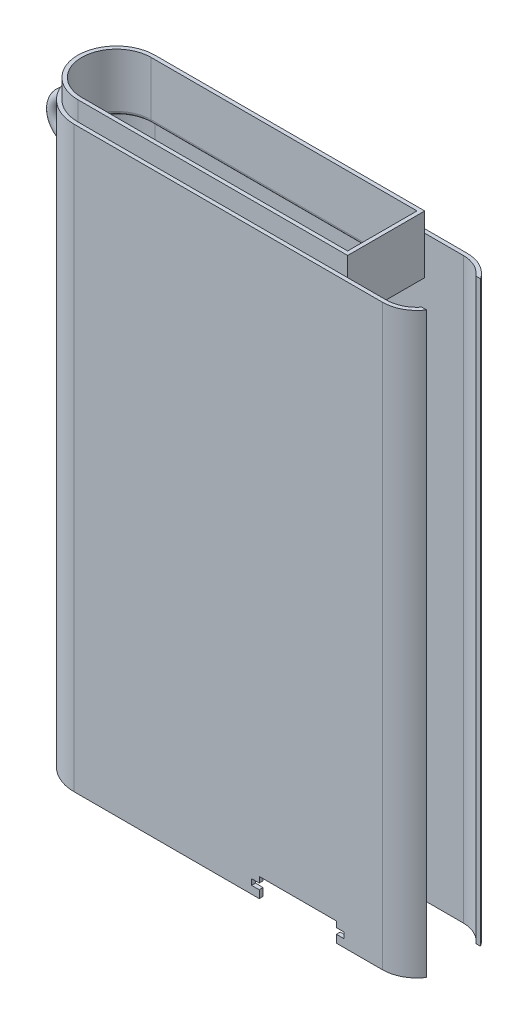
SolidWorks part; units mm, degrees
material "7075-O (SS)"
ref_plane "Front Plane" through (0, 0, 0) normal (0, 0, 1) x (1, 0, 0)
ref_plane "Top Plane" through (0, 0, 0) normal (0, 1, 0) x (1, 0, 0)
ref_plane "Right Plane" through (0, 0, 0) normal (1, 0, 0) x (0, 0, -1)
sketch "Sketch3" plane through (0, 0, 0) normal (0, 1, 0) x (1, 0, 0)
  line L0 (-97.3006, 0) -> (97.3006, 0) construction
  line L1 (0, 66.3624) -> (0, -66.3624) construction
  line L2 (0, 11) -> (80, 11)
  line L3 (0, 10) -> (80, 10)
  line L4 (86.245, 7) -> (87.4833, 7)
  line L5 (0, -10) -> (80, -10)
  line L6 (0, -11) -> (80, -11)
  line L7 (86.245, -7) -> (87.4833, -7)
  line L8 (80, 13.4664) -> (80, -11.4843) construction
  line L9 (86.245, 7) -> (86.245, -7) construction
  line L10 (87.4833, 7) -> (87.4833, -7) construction
  arc A0 (0, 11) -> (0, -11) centre (0, 0) ccw
  arc A1 (0, 10) -> (0, -10) centre (0, 0) ccw
  arc A2 (80, 10) -> (86.245, 7) centre (80, 2) cw
  arc A3 (80, 11) -> (87.4833, 7) centre (80, 2) cw
  arc A4 (80, -10) -> (86.245, -7) centre (80, -2) ccw
  arc A5 (80, -11) -> (87.4833, -7) centre (80, -2) ccw
  dimension "D1" = 11
  dimension "D2" = 10
  dimension "D4" = 8
  dimension "D5" = 9
  dimension "D7" = 8
  dimension "D8" = 9
  dimension "D3" = 80
  dimension "D6" = 7
  dimension "D9" = 7
extrude "Boss-Extrude1" add sketch "Sketch3" along normal blind 150
ref_plane "Plane1" through (0, 140, 0) normal (0, 1, 0) x (1, 0, 0)
sketch "Sketch4" plane through (0, 140, 0) normal (0, 1, 0) x (1, 0, 0)
  line L0 (0, 66.3624) -> (0, -66.3624) construction
  line L1 (0, 10) -> (70, 10)
  line L2 (0, -10) -> (70, -10)
  line L3 (0, 10) -> (80, 10) construction
  line L4 (0, -10) -> (80, -10) construction
  line L5 (70, 10) -> (70, -10)
  line L6 (0, 9) -> (69, 9)
  line L7 (0, -9) -> (69, -9)
  line L8 (69, -9) -> (69, 9)
  arc A0 (0, 10) -> (0, -10) centre (0, 0) ccw
  arc A1 (0, 9) -> (0, -9) centre (0, 0) ccw
  dimension "D3" = 9
  dimension "D1" = 70
  dimension "D2" = 70
  dimension "D4" = 69
extrude "Boss-Extrude2" add sketch "Sketch4" along normal blind 15 separate body
fillet "Fillet9" radius 1 3 edges at (34.5, 140, 9) (-9, 140, 0) (34.5, 140, -9)
sketch "Sketch7" plane through (0, 0, 11) normal (0, 0, 1) x (1, 0, 0)
  line L0 (48.0657, 0) -> (68.0657, 0)
  line L1 (0, 0) -> (80, 0) construction
  line L2 (68.0657, 0) -> (68.0657, 2)
  line L3 (68.0657, 2) -> (70.0657, 2)
  line L4 (70.0657, 2) -> (70.0657, 3.5)
  line L5 (70.0657, 3.5) -> (68.0657, 3.5)
  line L6 (68.0657, 3.5) -> (68.0657, 5)
  line L7 (68.0657, 5) -> (48.0657, 5)
  line L8 (48.0657, 5) -> (48.0657, 3.5)
  line L9 (48.0657, 3.5) -> (46.0657, 3.5)
  line L10 (46.0657, 3.5) -> (46.0657, 2)
  line L11 (46.0657, 2) -> (48.0657, 2)
  line L12 (48.0657, 2) -> (48.0657, 0)
  point P4 (58.0657, 0)
  point P15 (48.0657, 1)
  dimension "D1" = 20
  dimension "D2" = 20
  dimension "D3" = 1.5
  dimension "D4" = 1.5
  dimension "D5" = 5
  dimension "D6" = 2
  dimension "D7" = 2
  dimension "D8" = 2
  dimension "D9" = 2
  dimension "D10" = 1.5
  dimension "D11" = 1.5
  dimension "D12" = 48.0657
extrude "Cut-Extrude1" cut sketch "Sketch7" against normal blind 21 and the other way through all contours L7 L8 L9 L10 L11 L12 L0 L2 L3 L4 L5 L6
sketch "Sketch9" plane through (0, 0, 0) normal (0, 0, 1) x (1, 0, 0)
  line L0 (-11, 150) -> (-11, 0) construction
  arc A0 (-11, 145) -> (-11, 135) centre (-11, 140) ccw
  dimension "D1" = 5
  dimension "D2" = 10
sweep "Sweep1" add path "Sketch9" circular profile diameter 3 parameters "D3"=3
